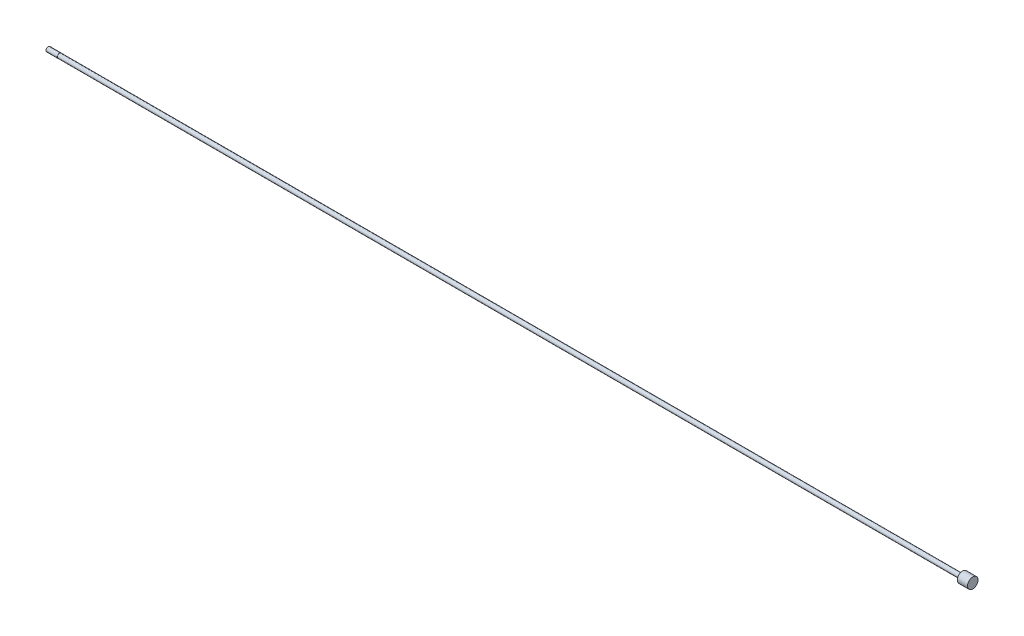
SolidWorks part; units mm, degrees
material "AISI 304"
ref_plane "Front Plane" through (0, 0, 0) normal (0, 0, 1) x (1, 0, 0)
ref_plane "Top Plane" through (0, 0, 0) normal (0, 1, 0) x (1, 0, 0)
ref_plane "Right Plane" through (0, 0, 0) normal (1, 0, 0) x (0, 0, -1)
sketch "Sketch1" plane through (0, 0, 0) normal (0, 0, 1) x (1, 0, 0)
  line L0 (0, 0) -> (0, 2.3749)
  line L1 (0, 2.3749) -> (969.9752, 2.3749)
  line L2 (969.9752, 2.3749) -> (969.9752, 5.6197)
  line L3 (969.9752, 5.6197) -> (980.9988, 5.6197)
  line L4 (980.9988, 5.6197) -> (980.9988, 0)
  line L5 (980.9988, 0) -> (0, 0)
  line L6 (980.9988, 0) -> (0, 0) construction
revolve "Revolve1" add sketch "Sketch1" angle 360 about L6 reverse direction yes
sketch "Sketch2" plane through (0, 0, 0) normal (0, 0, 1) x (1, 0, 0)
  line L0 (-12.7, 0) -> (-12.7, 1.9406)
  line L1 (-12.7, 1.9406) -> (-12.2276, 2.413)
  line L2 (-12.2276, 2.413) -> (0, 2.413)
  line L3 (0, 2.413) -> (0, 0)
  line L4 (0, 0) -> (-12.7, 0)
  line L5 (0, 0) -> (-12.7, 0) construction
revolve "Revolve2" add sketch "Sketch2" angle 360 about L5 reverse direction yes
cosmetic thread "Cosmetic Thread1" parameters "D1"=12.7, "D2"=3.8811
ref_plane "Plane1" through (0, 0, 0) normal (1, 0, 0) x (0, 0, -1)
ref_plane "Plane2" through (0, 0, 0) normal (1, 0, 0) x (0, 0, -1)
ref_plane "Plane3" through (1950.974, 0, 0) normal (1, 0, 0) x (0, 0, -1)
ref_plane "Plane4" through (-12.7, 0, 0) normal (1, 0, 0) x (0, 0, -1)
sketch "Sketch3" plane through (0, 0, 0) normal (0, 0, 1) x (1, 0, 0)
  line L0 (-0.254, 2.667) -> (-0.254, 2.159)
  line L1 (-0.254, 2.159) -> (0, 2.159)
  line L2 (0, 2.159) -> (0, 2.667)
  line L3 (0, 2.667) -> (-0.254, 2.667)
  line L4 (0, 0) -> (-0.254, 0) construction
revolve "Cut-Revolve1" cut sketch "Sketch3" angle 360 about L4 reverse direction yes
ref_plane "Plane5" through (0, 0, 0) normal (1, 0, 0) x (0, 0, -1)
ref_plane "Plane6" through (-12.7, 0, 0) normal (1, 0, 0) x (0, 0, -1)
ref_plane "dia1 XY" through (0, 0, 0) normal (1, 0, 0) x (0, 0, -1)
ref_plane "dia1 XZ" through (0, 2.3749, 0) normal (0, -1, 0) x (-1, 0, 0)
ref_plane "dia1 YZ" through (0, 0, 0) normal (0, 0, -1) x (-1, 0, 0)
ref_axis "dia1 X" through (0, 2.3749, 80.9) along (0, 0, -1)
ref_axis "dia1 Y" through (0, -50, 0) along (0, 1, 0)
ref_axis "dia1 Z" through (80.9, 2.3749, 0) along (-1, 0, 0)
sketch3d "dia1"
  point P0 (0, 2.3749, 0)
ref_plane "dia12 XY" through (0, 0, 0) normal (1, 0, 0) x (0, 0, -1)
ref_plane "dia12 XZ" through (0, 0, 0) normal (0, -1, 0) x (-1, 0, 0)
ref_plane "dia12 YZ" through (0, 0, 9.3726) normal (0, 0, -1) x (-1, 0, 0)
ref_axis "dia12 X" through (0, 0, 80.9) along (0, 0, -1)
ref_axis "dia12 Y" through (0, -50, 9.3726) along (0, 1, 0)
ref_axis "dia12 Z" through (80.9, 0, 9.3726) along (-1, 0, 0)
sketch3d "dia12"
  point P0 (0, 0, 9.3726)
ref_plane "dia2 XY" through (0, 0, 0) normal (1, 0, 0) x (0, 0, -1)
ref_plane "dia2 XZ" through (0, -2.3749, 0) normal (0, -1, 0) x (-1, 0, 0)
ref_plane "dia2 YZ" through (0, 0, 0) normal (0, 0, -1) x (-1, 0, 0)
ref_axis "dia2 X" through (0, -2.3749, 80.9) along (0, 0, -1)
ref_axis "dia2 Y" through (0, -50, 0) along (0, 1, 0)
ref_axis "dia2 Z" through (80.9, -2.3749, 0) along (-1, 0, 0)
sketch3d "dia2"
  point P0 (0, -2.3749, 0)
ref_plane "dia22 XY" through (0, 0, 0) normal (1, 0, 0) x (0, 0, -1)
ref_plane "dia22 XZ" through (0, 0, 0) normal (0, -1, 0) x (-1, 0, 0)
ref_plane "dia22 YZ" through (0, 0, -9.3726) normal (0, 0, -1) x (-1, 0, 0)
ref_axis "dia22 X" through (0, 0, 80.9) along (0, 0, -1)
ref_axis "dia22 Y" through (0, -50, -9.3726) along (0, 1, 0)
ref_axis "dia22 Z" through (80.9, 0, -9.3726) along (-1, 0, 0)
sketch3d "dia22"
  point P0 (0, 0, -9.3726)
ref_plane "rl1 XY" through (-12.7, 0, 0) normal (1, 0, 0) x (0, 0, -1)
ref_plane "rl1 XZ" through (0, 0, 0) normal (0, -1, 0) x (-1, 0, 0)
ref_plane "rl1 YZ" through (0, 0, 0) normal (0, 0, -1) x (-1, 0, 0)
ref_axis "rl1 X" through (-12.7, 0, 80.9) along (0, 0, -1)
ref_axis "rl1 Y" through (-12.7, -50, 0) along (0, 1, 0)
ref_axis "rl1 Z" through (80.9, 0, 0) along (-1, 0, 0)
sketch3d "rl1"
  point P0 (-12.7, 0, 0)
ref_plane "rl2 XY" through (0, 0, 0) normal (1, 0, 0) x (0, 0, -1)
ref_plane "rl2 XZ" through (0, 0, 0) normal (0, -1, 0) x (-1, 0, 0)
ref_plane "rl2 YZ" through (0, 0, 0) normal (0, 0, -1) x (-1, 0, 0)
ref_axis "rl2 X" through (0, 0, 80.9) along (0, 0, -1)
ref_axis "rl2 Y" through (0, -50, 0) along (0, 1, 0)
ref_axis "rl2 Z" through (80.9, 0, 0) along (-1, 0, 0)
sketch3d "rl2"
  point P0 (0, 0, 0)
ref_plane "rod_cp XY" through (0, 0, 0) normal (1, 0, 0) x (0, 0, -1)
ref_plane "rod_cp XZ" through (0, 0, 0) normal (0, -1, 0) x (-1, 0, 0)
ref_plane "rod_cp YZ" through (0, 0, 0) normal (0, 0, -1) x (-1, 0, 0)
ref_axis "rod_cp X" through (0, 0, 80.9) along (0, 0, -1)
ref_axis "rod_cp Y" through (0, -50, 0) along (0, 1, 0)
ref_axis "rod_cp Z" through (80.9, 0, 0) along (-1, 0, 0)
sketch3d "rod_cp"
  point P0 (0, 0, 0)
ref_plane "thd1 XY" through (-12.7, 0, 0) normal (1, 0, 0) x (0, 0, -1)
ref_plane "thd1 XZ" through (0, 2.413, 0) normal (0, -1, 0) x (-1, 0, 0)
ref_plane "thd1 YZ" through (0, 0, 0) normal (0, 0, -1) x (-1, 0, 0)
ref_axis "thd1 X" through (-12.7, 2.413, 80.9) along (0, 0, -1)
ref_axis "thd1 Y" through (-12.7, -50, 0) along (0, 1, 0)
ref_axis "thd1 Z" through (80.9, 2.413, 0) along (-1, 0, 0)
sketch3d "thd1"
  point P0 (-12.7, 2.413, 0)
ref_plane "thd2 XY" through (-12.7, 0, 0) normal (1, 0, 0) x (0, 0, -1)
ref_plane "thd2 XZ" through (0, -2.413, 0) normal (0, -1, 0) x (-1, 0, 0)
ref_plane "thd2 YZ" through (0, 0, 0) normal (0, 0, -1) x (-1, 0, 0)
ref_axis "thd2 X" through (-12.7, -2.413, 80.9) along (0, 0, -1)
ref_axis "thd2 Y" through (-12.7, -50, 0) along (0, 1, 0)
ref_axis "thd2 Z" through (80.9, -2.413, 0) along (-1, 0, 0)
sketch3d "thd2"
  point P0 (-12.7, -2.413, 0)
ref_plane "to_rod_clevis XY" through (-12.7, 0, 0) normal (1, 0, 0) x (0, 0, -1)
ref_plane "to_rod_clevis XZ" through (0, 0, 0) normal (0, -1, 0) x (-1, 0, 0)
ref_plane "to_rod_clevis YZ" through (0, 0, 0) normal (0, 0, -1) x (-1, 0, 0)
ref_axis "to_rod_clevis X" through (-12.7, 0, 80.9) along (0, 0, -1)
ref_axis "to_rod_clevis Y" through (-12.7, -50, 0) along (0, 1, 0)
ref_axis "to_rod_clevis Z" through (80.9, 0, 0) along (-1, 0, 0)
sketch3d "to_rod_clevis"
  point P0 (-12.7, 0, 0)
